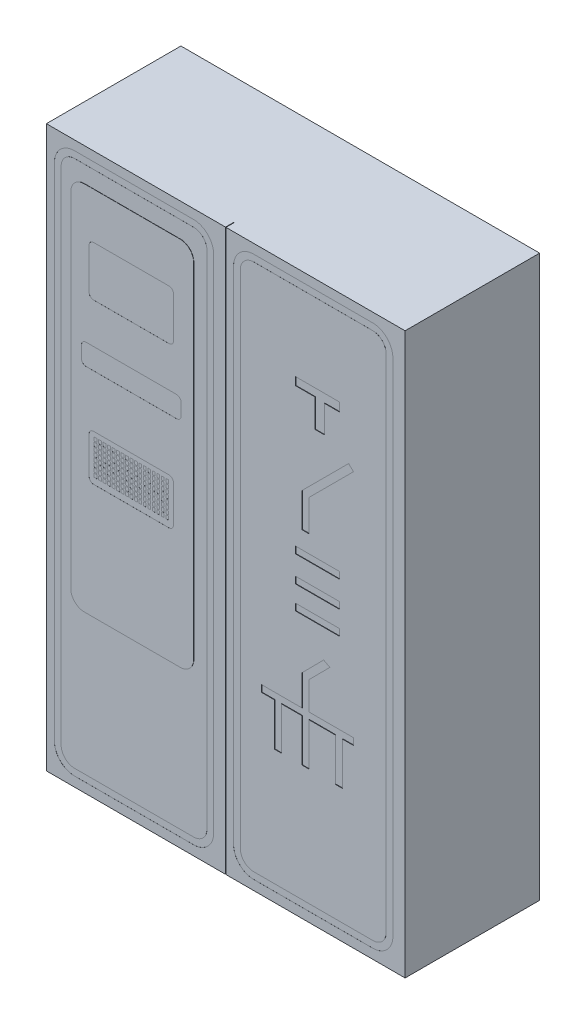
SolidWorks part; units mm, degrees
ref_plane "Alzado" through (0, 0, 0) normal (0, 0, 1) x (1, 0, 0)
ref_plane "Planta" through (0, 0, 0) normal (0, 1, 0) x (1, 0, 0)
ref_plane "Vista lateral" through (0, 0, 0) normal (1, 0, 0) x (0, 0, -1)
sketch "Croquis1" plane through (0, 0, 0) normal (0, 1, 0) x (1, 0, 0)
  line L1 (-800, 300) -> (800, 300)
  line L2 (-800, 300) -> (-800, -300)
  line L3 (-800, -300) -> (800, -300)
  line L4 (800, 300) -> (800, -300)
  line L5 (-800, 300) -> (800, -300) construction
  line L6 (-800, -300) -> (800, 300) construction
  point P0 (0, 0)
  dimension "D1" = 1600
  dimension "D2" = 600
extrude "Saliente-Extruir1" add sketch "Croquis1" along normal blind 2500
sketch "Croquis2" plane through (0, 0, 300) normal (0, 0, 1) x (1, 0, 0)
  line L0 (-800, 0) -> (800, 0) construction
  line L1 (800, 0) -> (0, 0) construction
  line L2 (0, 0) -> (0, 2500) construction
  line L3 (-800, 2500) -> (800, 2500) construction
  line L5 (-1, 2500) -> (1, 2500)
  line L6 (-1, 2500) -> (-1, 0)
  line L7 (-1, 0) -> (1, 0)
  line L8 (1, 2500) -> (1, 0)
  line L9 (-1, 2500) -> (1, 0) construction
  line L10 (-1, 0) -> (1, 2500) construction
  point P4 (0, 1250)
  dimension "D1" = 2
extrude "Cortar-Extruir1" cut sketch "Croquis2" against normal blind 38
sketch "Croquis3" plane through (0, 0, 300) normal (0, 0, 1) x (1, 0, 0)
  line L0 (-764.13, 2368.2469) -> (-764.13, 132.9173)
  line L1 (-674.13, 2428.2469) -> (-143.7099, 2428.2469)
  line L2 (-734.13, 2368.2469) -> (-734.13, 132.9173)
  line L3 (-674.13, 72.9173) -> (-143.7099, 72.9173)
  line L4 (-83.7099, 2368.2469) -> (-83.7099, 132.9173)
  line L5 (-734.13, 2428.2469) -> (-83.7099, 72.9173) construction
  line L6 (-734.13, 72.9173) -> (-83.7099, 2428.2469) construction
  line L7 (124.9525, 2428.2469) -> (655.4513, 2428.2469)
  line L8 (64.9525, 2368.2469) -> (64.9525, 132.9173)
  line L9 (124.9525, 72.9173) -> (655.4513, 72.9173)
  line L10 (715.4513, 2368.2469) -> (715.4513, 132.9173)
  line L11 (64.9525, 2428.2469) -> (715.4513, 72.9173) construction
  line L12 (64.9525, 72.9173) -> (715.4513, 2428.2469) construction
  line L13 (-674.13, 42.9173) -> (-143.7099, 42.9173)
  line L14 (-53.7099, 2368.2469) -> (-53.7099, 132.9173)
  line L15 (-674.13, 2458.2469) -> (-143.7099, 2458.2469)
  line L16 (34.9525, 2368.2469) -> (34.9525, 132.9173)
  line L17 (124.9525, 42.9173) -> (655.4513, 42.9173)
  line L18 (745.4513, 2368.2469) -> (745.4513, 132.9173)
  line L19 (124.9525, 2458.2469) -> (655.4513, 2458.2469)
  arc A0 (-734.13, 132.9173) -> (-674.13, 72.9173) centre (-674.13, 132.9173) ccw
  arc A1 (-143.7099, 72.9173) -> (-83.7099, 132.9173) centre (-143.7099, 132.9173) ccw
  arc A2 (-674.13, 2428.2469) -> (-734.13, 2368.2469) centre (-674.13, 2368.2469) ccw
  arc A3 (-143.7099, 2428.2469) -> (-83.7099, 2368.2469) centre (-143.7099, 2368.2469) cw
  arc A4 (655.4513, 72.9173) -> (715.4513, 132.9173) centre (655.4513, 132.9173) ccw
  arc A5 (64.9525, 132.9173) -> (124.9525, 72.9173) centre (124.9525, 132.9173) ccw
  arc A6 (124.9525, 2428.2469) -> (64.9525, 2368.2469) centre (124.9525, 2368.2469) ccw
  arc A7 (655.4513, 2428.2469) -> (715.4513, 2368.2469) centre (655.4513, 2368.2469) cw
  arc A8 (-764.13, 132.9173) -> (-674.13, 42.9173) centre (-674.13, 132.9173) ccw
  arc A9 (-143.7099, 42.9173) -> (-53.7099, 132.9173) centre (-143.7099, 132.9173) ccw
  arc A10 (-143.7099, 2458.2469) -> (-53.7099, 2368.2469) centre (-143.7099, 2368.2469) cw
  arc A11 (-674.13, 2458.2469) -> (-764.13, 2368.2469) centre (-674.13, 2368.2469) ccw
  arc A12 (34.9525, 132.9173) -> (124.9525, 42.9173) centre (124.9525, 132.9173) ccw
  arc A13 (655.4513, 42.9173) -> (745.4513, 132.9173) centre (655.4513, 132.9173) ccw
  arc A14 (655.4513, 2458.2469) -> (745.4513, 2368.2469) centre (655.4513, 2368.2469) cw
  arc A15 (124.9525, 2458.2469) -> (34.9525, 2368.2469) centre (124.9525, 2368.2469) ccw
  point P0 (-408.9199, 1250.5821)
  point P7 (390.2019, 1250.5821)
  point P58 (-408.9199, 1250.5821)
  point P59 (390.2019, 1250.5821)
  dimension "D1" = 60
  dimension "D2" = 60
  dimension "D3" = 30
extrude "Cortar-Extruir2" cut sketch "Croquis3" against normal blind 0.2
sketch "Croquis4" plane through (0, 0, 300) normal (0, 0, 1) x (1, 0, 0)
  line L1 (-630.0138, 2353.3504) -> (-202.1979, 2353.3504)
  line L2 (-690.0138, 2293.3504) -> (-690.0138, 759.4321)
  line L3 (-630.0138, 699.4321) -> (-202.1979, 699.4321)
  line L4 (-142.1979, 2293.3504) -> (-142.1979, 759.4321)
  line L5 (-690.0138, 2353.3504) -> (-142.1979, 699.4321) construction
  line L6 (-690.0138, 699.4321) -> (-142.1979, 2353.3504) construction
  arc A0 (-690.0138, 759.4321) -> (-630.0138, 699.4321) centre (-630.0138, 759.4321) ccw
  arc A1 (-202.1979, 699.4321) -> (-142.1979, 759.4321) centre (-202.1979, 759.4321) ccw
  arc A2 (-202.1979, 2353.3504) -> (-142.1979, 2293.3504) centre (-202.1979, 2293.3504) cw
  arc A3 (-630.0138, 2353.3504) -> (-690.0138, 2293.3504) centre (-630.0138, 2293.3504) ccw
  point P0 (-416.1058, 1526.3913)
  point P5 (-690.0138, 699.4321)
  point P6 (0, 0)
  dimension "D1" = 60
extrude "Saliente-Extruir2" add sketch "Croquis4" along normal blind 1
sketch "Croquis5" plane through (0, 0, 300) normal (0, 0, 1) x (1, 0, 0)
  line L0 (311.7998, 2078.6157) -> (507.1372, 2078.6157)
  line L1 (507.1372, 2078.6157) -> (507.1372, 2039.935)
  line L2 (507.1372, 2039.935) -> (439.446, 2039.935)
  line L3 (439.446, 2039.935) -> (439.446, 1918.0908)
  line L4 (439.446, 1918.0908) -> (397.3177, 1918.0908)
  line L5 (397.3177, 1918.0908) -> (397.3177, 2043.4837)
  line L6 (397.3177, 2043.4837) -> (311.7998, 2043.4837)
  line L7 (311.7998, 2043.4837) -> (311.7998, 2078.6157)
  line L8 (370.5926, 1501.6025) -> (370.5926, 1641.2081)
  line L9 (370.5926, 1641.2081) -> (569.5162, 1840.1318)
  line L10 (311.7998, 1394.0247) -> (507.1372, 1394.0247)
  line L11 (311.7998, 1277.7227) -> (507.1372, 1277.7227)
  line L12 (311.7998, 1173.452) -> (507.1372, 1173.452)
  line L13 (370.5926, 813.1386) -> (370.5926, 937.3816)
  line L14 (370.5926, 937.3816) -> (464.5629, 1032.1528)
  line L15 (158.7696, 783.1386) -> (217.6549, 783.1386)
  line L16 (340.5926, 1501.6025) -> (340.5926, 1653.6346)
  line L17 (340.5926, 1653.6346) -> (548.303, 1861.345)
  line L18 (311.7998, 1424.0247) -> (507.1372, 1424.0247)
  line L19 (311.7998, 1307.7227) -> (507.1372, 1307.7227)
  line L20 (311.7998, 1203.452) -> (507.1372, 1203.452)
  line L21 (340.5926, 813.1386) -> (340.5926, 949.7335)
  line L22 (340.5926, 949.7335) -> (436.6836, 1046.6435)
  line L23 (158.7696, 813.1386) -> (340.5926, 813.1386)
  line L24 (340.5926, 785.8374) -> (340.5926, 949.7335) construction
  line L25 (370.5926, 785.8374) -> (370.5926, 937.3816) construction
  line L26 (370.5926, 813.1386) -> (569.9498, 813.1386)
  line L27 (158.7696, 813.1386) -> (569.9498, 813.1386) construction
  line L28 (158.7696, 783.1386) -> (569.9498, 783.1386) construction
  line L29 (370.5926, 937.3816) -> (551.2929, 1119.6219) construction
  line L30 (340.5926, 949.7335) -> (529.9898, 1140.7449) construction
  line L31 (436.6836, 1046.6435) -> (464.5629, 1032.1528)
  line L32 (569.9498, 813.1386) -> (569.9498, 783.1386)
  line L33 (158.7696, 813.1386) -> (158.7696, 783.1386)
  line L34 (340.5926, 1501.6025) -> (370.5926, 1501.6025)
  line L35 (548.303, 1861.345) -> (569.5162, 1840.1318)
  line L36 (507.1372, 1424.0247) -> (507.1372, 1394.0247)
  line L37 (311.7998, 1424.0247) -> (311.7998, 1394.0247)
  line L38 (311.7998, 1307.7227) -> (311.7998, 1277.7227)
  line L39 (311.7998, 1203.452) -> (311.7998, 1173.452)
  line L40 (507.1372, 1307.7227) -> (507.1372, 1277.7227)
  line L41 (507.1372, 1203.452) -> (507.1372, 1173.452)
  line L42 (217.6549, 783.1386) -> (217.6549, 592.6653)
  line L43 (217.6549, 592.6653) -> (247.9131, 592.6653)
  line L44 (247.9131, 592.6653) -> (247.9131, 783.1386)
  line L45 (340.5926, 783.1386) -> (340.5926, 592.6653)
  line L46 (340.5926, 592.6653) -> (370.5926, 592.6653)
  line L47 (370.5926, 592.6653) -> (370.5926, 783.1386)
  line L48 (488.5221, 783.1386) -> (488.5221, 592.6653)
  line L49 (488.5221, 592.6653) -> (521.2342, 592.6653)
  line L50 (521.2342, 592.6653) -> (521.2342, 783.1386)
  line L51 (247.9131, 783.1386) -> (340.5926, 783.1386)
  line L52 (370.5926, 783.1386) -> (488.5221, 783.1386)
  line L53 (521.2342, 783.1386) -> (569.9498, 783.1386)
  dimension "D1" = 30
extrude "Cortar-Extruir3" cut sketch "Croquis5" against normal blind 2
sketch "Croquis6" plane through (0, 0, 301) normal (0, 0, 1) x (1, 0, 0)
  line L1 (-588.3994, 2147.5088) -> (-252.1279, 2147.5088)
  line L2 (-608.3994, 2127.5088) -> (-608.3994, 1945.0223)
  line L3 (-588.3994, 1925.0223) -> (-252.1279, 1925.0223)
  line L4 (-232.1279, 2127.5088) -> (-232.1279, 1945.0223)
  line L5 (-608.3994, 2147.5088) -> (-232.1279, 1925.0223) construction
  line L6 (-608.3994, 1925.0223) -> (-232.1279, 2147.5088) construction
  line L7 (-622.3572, 1745.3998) -> (-218.1701, 1745.3998)
  line L8 (-642.3572, 1725.3998) -> (-642.3572, 1671.59)
  line L9 (-622.3572, 1651.59) -> (-218.1701, 1651.59)
  line L10 (-198.1701, 1725.3998) -> (-198.1701, 1671.59)
  line L11 (-642.3572, 1745.3998) -> (-198.1701, 1651.59) construction
  line L12 (-642.3572, 1651.59) -> (-198.1701, 1745.3998) construction
  line L13 (-588.3994, 1417.9003) -> (-252.1279, 1417.9003)
  line L14 (-608.3994, 1397.9003) -> (-608.3994, 1233.065)
  line L15 (-588.3994, 1213.065) -> (-252.1279, 1213.065)
  line L16 (-232.1279, 1397.9003) -> (-232.1279, 1233.065)
  line L17 (-608.3994, 1417.9003) -> (-232.1279, 1213.065) construction
  line L18 (-608.3994, 1213.065) -> (-232.1279, 1417.9003) construction
  arc A0 (-588.3994, 1417.9003) -> (-608.3994, 1397.9003) centre (-588.3994, 1397.9003) ccw
  arc A1 (-608.3994, 1233.065) -> (-588.3994, 1213.065) centre (-588.3994, 1233.065) ccw
  arc A2 (-252.1279, 1213.065) -> (-232.1279, 1233.065) centre (-252.1279, 1233.065) ccw
  arc A3 (-252.1279, 1417.9003) -> (-232.1279, 1397.9003) centre (-252.1279, 1397.9003) cw
  arc A4 (-642.3572, 1671.59) -> (-622.3572, 1651.59) centre (-622.3572, 1671.59) ccw
  arc A5 (-622.3572, 1745.3998) -> (-642.3572, 1725.3998) centre (-622.3572, 1725.3998) ccw
  arc A6 (-218.1701, 1651.59) -> (-198.1701, 1671.59) centre (-218.1701, 1671.59) ccw
  arc A7 (-218.1701, 1745.3998) -> (-198.1701, 1725.3998) centre (-218.1701, 1725.3998) cw
  arc A8 (-252.1279, 1925.0223) -> (-232.1279, 1945.0223) centre (-252.1279, 1945.0223) ccw
  arc A9 (-608.3994, 1945.0223) -> (-588.3994, 1925.0223) centre (-588.3994, 1945.0223) ccw
  arc A10 (-588.3994, 2147.5088) -> (-608.3994, 2127.5088) centre (-588.3994, 2127.5088) ccw
  arc A11 (-252.1279, 2147.5088) -> (-232.1279, 2127.5088) centre (-252.1279, 2127.5088) cw
  point P0 (-420.2637, 2036.2655)
  point P5 (-420.2637, 1315.4827)
  point P7 (-420.2637, 1698.4949)
  dimension "D1" = 20
extrude "Cortar-Extruir4" cut sketch "Croquis6" against normal blind 0.2
sketch "Croquis7" plane through (0, 0, 300.8) normal (0, 0, 1) x (1, 0, 0)
  line L1 (-586.2098, 1397.2771) -> (-573.825, 1397.2771)
  line L2 (-586.2098, 1397.2771) -> (-586.2098, 1381.5146)
  line L3 (-586.2098, 1381.5146) -> (-573.825, 1381.5146)
  line L4 (-573.825, 1397.2771) -> (-573.825, 1381.5146)
  line L5 (-586.2098, 1397.2771) -> (-573.825, 1381.5146) construction
  line L6 (-586.2098, 1381.5146) -> (-573.825, 1397.2771) construction
  point P0 (-580.0174, 1389.3958)
extrude "Cortar-Extruir5" cut sketch "Croquis7" against normal blind 0.1
pattern_linear "MatrizL1" count 17 spacing 20 along (1, 0, 0) of "Cortar-Extruir5"
pattern_linear "MatrizL2" count 8 spacing 20 along (0, -1, 0) of "MatrizL1"
